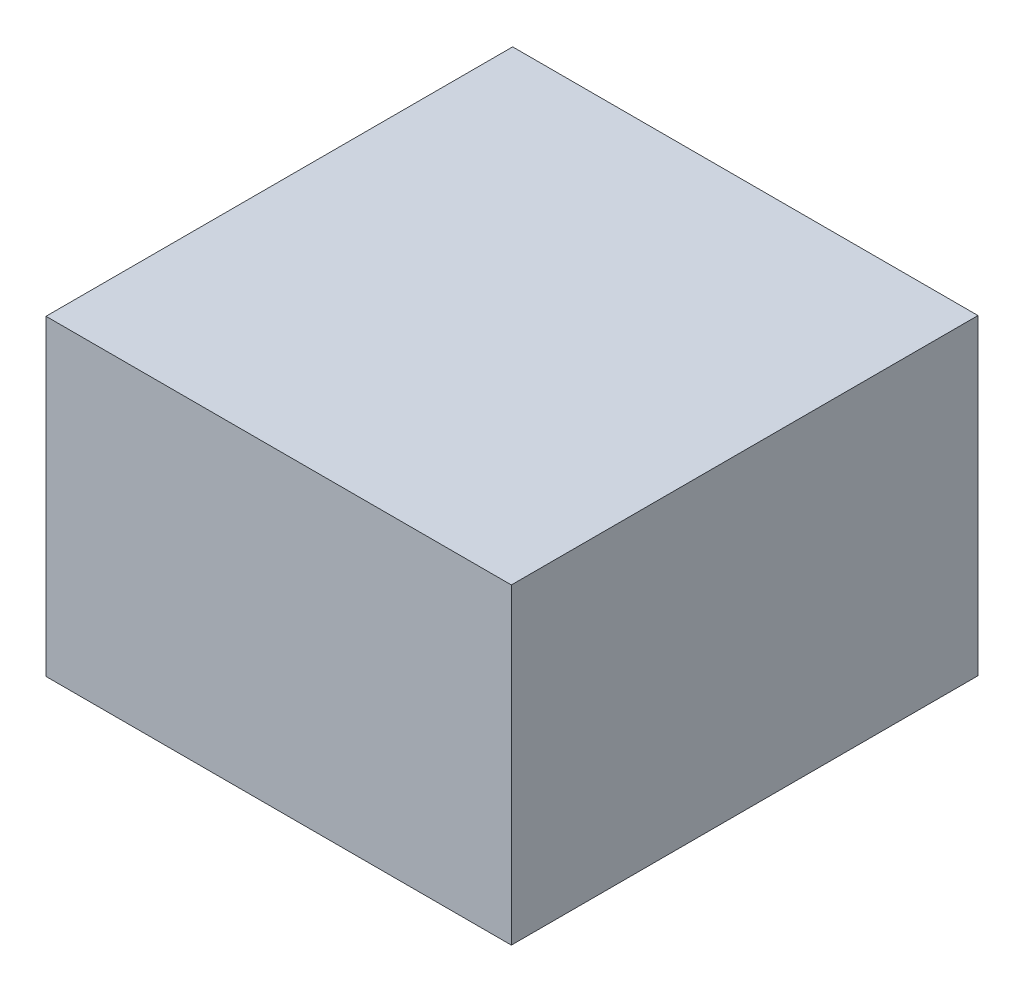
SolidWorks part; units mm, degrees
ref_plane "Front Plane" through (0, 0, 0) normal (0, 0, 1) x (1, 0, 0)
ref_plane "Top Plane" through (0, 0, 0) normal (0, 1, 0) x (1, 0, 0)
ref_plane "Right Plane" through (0, 0, 0) normal (1, 0, 0) x (0, 0, -1)
sketch "Sketch2" plane through (0, 0, 0) normal (0, 0, 1) x (1, 0, 0)
  line L1 (-457.2, 0) -> (457.2, 0)
  line L2 (-457.2, 0) -> (-457.2, 609.6)
  line L3 (-457.2, 609.6) -> (457.2, 609.6)
  line L4 (457.2, 0) -> (457.2, 609.6)
  dimension "D1" = 914.4
  dimension "D2" = 609.6
extrude "Boss-Extrude1" add sketch "Sketch2" along normal blind 914.4
shell "Shell2" thickness 2.54 removed face at (-457.2, 304.8, 457.2) outward yes
equation "\"W\"=36"
equation "\"D1@Sketch2\"=\"W\""
equation "\"H\" = 24"
equation "\"D2@Sketch2\"=\"H\""
equation "\"L\"=36"
equation "\"D1@Boss-Extrude1\"=\"L\""
